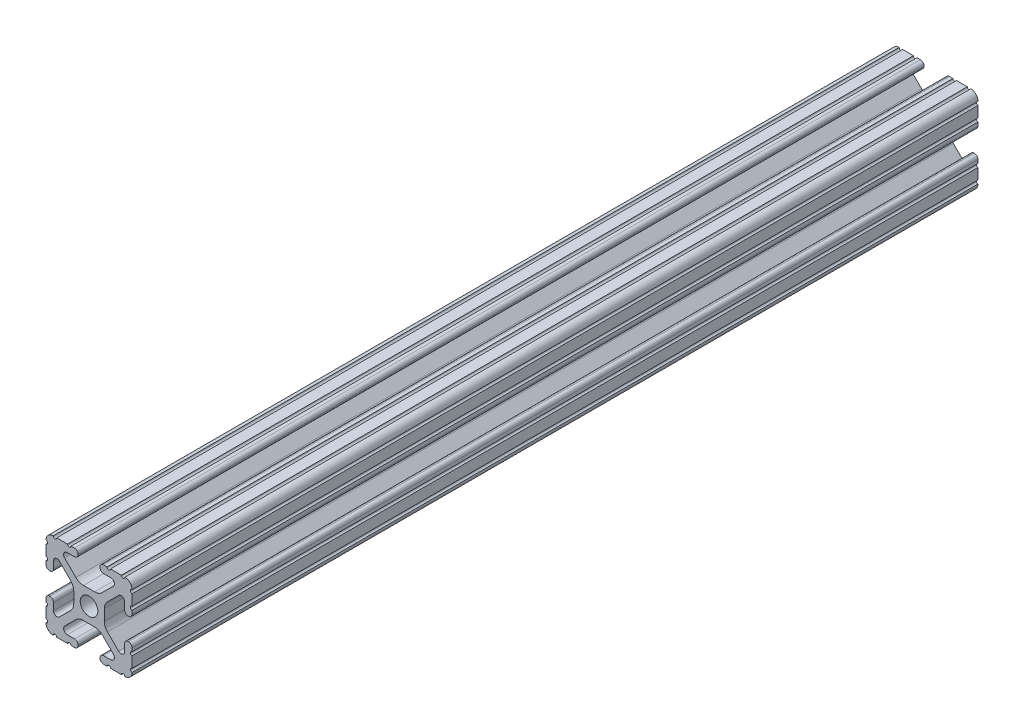
SolidWorks part; units mm, degrees
ref_plane "Front Plane" through (0, 0, 0) normal (0, 0, 1) x (1, 0, 0)
ref_plane "Top Plane" through (0, 0, 0) normal (0, 1, 0) x (1, 0, 0)
ref_plane "Right Plane" through (0, 0, 0) normal (1, 0, 0) x (0, 0, -1)
sketch "Sketch1" plane through (0, 0, 0) normal (0, 0, 1) x (1, 0, 0)
  line L88 (-7.1797, -8.6452) -> (-3.9523, -5.4237)
  line L89 (-1.7093, -4.4958) -> (1.7093, -4.4958)
  line L90 (3.9523, -5.4237) -> (7.1797, -8.6452)
  line L91 (6.4164, -10.4902) -> (4.2875, -10.4902)
  line L92 (3.2385, -11.5392) -> (3.2385, -11.651)
  line L93 (4.2875, -12.7) -> (5.3171, -12.7)
  line L94 (6.3331, -12.7) -> (9.5504, -12.7)
  line L95 (12.7, -9.5504) -> (12.7, -6.3331)
  line L96 (12.7, -5.3171) -> (12.7, -4.2875)
  line L97 (11.651, -3.2385) -> (11.5392, -3.2385)
  line L98 (10.4902, -4.2875) -> (10.4902, -6.4021)
  line L99 (8.7371, -7.1294) -> (5.441, -3.8408)
  line L100 (4.5085, -1.5932) -> (4.5085, 1.5932)
  line L101 (5.441, 3.8408) -> (8.7371, 7.1294)
  line L102 (10.4902, 6.4021) -> (10.4902, 4.2875)
  line L103 (11.5392, 3.2385) -> (11.651, 3.2385)
  line L104 (12.7, 4.2875) -> (12.7, 5.3171)
  line L105 (12.7, 6.3331) -> (12.7, 9.5504)
  line L106 (9.5504, 12.7) -> (6.3331, 12.7)
  line L107 (5.3171, 12.7) -> (4.2875, 12.7)
  line L108 (3.2385, 11.651) -> (3.2385, 11.5392)
  line L109 (4.2875, 10.4902) -> (6.4768, 10.4902)
  line L110 (7.207, 8.7244) -> (3.8983, 5.4232)
  line L111 (1.6558, 4.4958) -> (-1.6558, 4.4958)
  line L112 (-3.8983, 5.4232) -> (-7.207, 8.7244)
  line L113 (-6.4768, 10.4902) -> (-4.2875, 10.4902)
  line L114 (-3.2385, 11.5392) -> (-3.2385, 11.651)
  line L115 (-4.2875, 12.7) -> (-5.3171, 12.7)
  line L116 (-6.3331, 12.7) -> (-9.5504, 12.7)
  line L117 (-12.7, 9.5504) -> (-12.7, 6.3331)
  line L118 (-12.7, 5.3171) -> (-12.7, 4.2875)
  line L119 (-11.651, 3.2385) -> (-11.5392, 3.2385)
  line L120 (-10.4902, 4.2875) -> (-10.4902, 6.4021)
  line L121 (-8.7371, 7.1294) -> (-5.441, 3.8408)
  line L122 (-4.5085, 1.5932) -> (-4.5085, -1.5932)
  line L123 (-5.441, -3.8408) -> (-8.7371, -7.1294)
  line L124 (-10.4902, -6.4021) -> (-10.4902, -4.2875)
  line L125 (-11.5392, -3.2385) -> (-11.651, -3.2385)
  line L126 (-12.7, -4.2875) -> (-12.7, -5.3171)
  line L127 (-12.7, -6.3331) -> (-12.7, -9.5504)
  line L128 (-9.5504, -12.7) -> (-6.3331, -12.7)
  line L129 (-5.3171, -12.7) -> (-4.2875, -12.7)
  line L130 (-3.2385, -11.651) -> (-3.2385, -11.5392)
  line L131 (-4.2875, -10.4902) -> (-6.4164, -10.4902)
  circle A1 centre (0, 0) radius 2.6035
  arc A104 (-7.1797, -8.6452) -> (-6.4164, -10.4902) centre (-6.4164, -9.4098) ccw
  arc A105 (-1.7093, -4.4958) -> (-3.9523, -5.4237) centre (-1.7093, -7.6708) ccw
  arc A106 (3.9523, -5.4237) -> (1.7093, -4.4958) centre (1.7093, -7.6708) ccw
  arc A107 (6.4164, -10.4902) -> (7.1797, -8.6452) centre (6.4164, -9.4098) ccw
  arc A108 (4.2875, -10.4902) -> (3.2385, -11.5392) centre (4.2875, -11.5392) ccw
  arc A109 (3.2385, -11.651) -> (4.2875, -12.7) centre (4.2875, -11.651) ccw
  arc A110 (6.3331, -12.7) -> (5.3171, -12.7) centre (5.8251, -12.7) ccw
  arc A111 (10.5664, -12.6998) -> (9.5504, -12.7) centre (10.0584, -12.7) ccw
  arc A112 (10.5664, -12.6998) -> (12.6998, -10.5664) centre (10.5918, -10.5918) ccw
  arc A113 (12.7, -9.5504) -> (12.6998, -10.5664) centre (12.7, -10.0584) ccw
  arc A114 (12.7, -5.3171) -> (12.7, -6.3331) centre (12.7, -5.8251) ccw
  arc A115 (12.7, -4.2875) -> (11.651, -3.2385) centre (11.651, -4.2875) ccw
  arc A116 (11.5392, -3.2385) -> (10.4902, -4.2875) centre (11.5392, -4.2875) ccw
  arc A117 (8.7371, -7.1294) -> (10.4902, -6.4021) centre (9.4628, -6.4021) ccw
  arc A118 (4.5085, -1.5932) -> (5.441, -3.8408) centre (7.6835, -1.5932) ccw
  arc A119 (5.441, 3.8408) -> (4.5085, 1.5932) centre (7.6835, 1.5932) ccw
  arc A120 (10.4902, 6.4021) -> (8.7371, 7.1294) centre (9.4628, 6.4021) ccw
  arc A121 (10.4902, 4.2875) -> (11.5392, 3.2385) centre (11.5392, 4.2875) ccw
  arc A122 (11.651, 3.2385) -> (12.7, 4.2875) centre (11.651, 4.2875) ccw
  arc A123 (12.7, 6.3331) -> (12.7, 5.3171) centre (12.7, 5.8251) ccw
  arc A124 (12.6998, 10.5664) -> (12.7, 9.5504) centre (12.7, 10.0584) ccw
  arc A125 (12.6998, 10.5664) -> (10.5664, 12.6998) centre (10.5918, 10.5918) ccw
  arc A126 (9.5504, 12.7) -> (10.5664, 12.6998) centre (10.0584, 12.7) ccw
  arc A127 (5.3171, 12.7) -> (6.3331, 12.7) centre (5.8251, 12.7) ccw
  arc A128 (4.2875, 12.7) -> (3.2385, 11.651) centre (4.2875, 11.651) ccw
  arc A129 (3.2385, 11.5392) -> (4.2875, 10.4902) centre (4.2875, 11.5392) ccw
  arc A130 (7.207, 8.7244) -> (6.4768, 10.4902) centre (6.4768, 9.4563) ccw
  arc A131 (1.6558, 4.4958) -> (3.8983, 5.4232) centre (1.6558, 7.6708) ccw
  arc A132 (-3.8983, 5.4232) -> (-1.6558, 4.4958) centre (-1.6558, 7.6708) ccw
  arc A133 (-6.4768, 10.4902) -> (-7.207, 8.7244) centre (-6.4768, 9.4563) ccw
  arc A134 (-4.2875, 10.4902) -> (-3.2385, 11.5392) centre (-4.2875, 11.5392) ccw
  arc A135 (-3.2385, 11.651) -> (-4.2875, 12.7) centre (-4.2875, 11.651) ccw
  arc A136 (-6.3331, 12.7) -> (-5.3171, 12.7) centre (-5.8251, 12.7) ccw
  arc A137 (-10.5664, 12.6998) -> (-9.5504, 12.7) centre (-10.0584, 12.7) ccw
  arc A138 (-10.5664, 12.6998) -> (-12.6998, 10.5664) centre (-10.5918, 10.5918) ccw
  arc A139 (-12.7, 9.5504) -> (-12.6998, 10.5664) centre (-12.7, 10.0584) ccw
  arc A140 (-12.7, 5.3171) -> (-12.7, 6.3331) centre (-12.7, 5.8251) ccw
  arc A141 (-12.7, 4.2875) -> (-11.651, 3.2385) centre (-11.651, 4.2875) ccw
  arc A142 (-11.5392, 3.2385) -> (-10.4902, 4.2875) centre (-11.5392, 4.2875) ccw
  arc A143 (-8.7371, 7.1294) -> (-10.4902, 6.4021) centre (-9.4628, 6.4021) ccw
  arc A144 (-4.5085, 1.5932) -> (-5.441, 3.8408) centre (-7.6835, 1.5932) ccw
  arc A145 (-5.441, -3.8408) -> (-4.5085, -1.5932) centre (-7.6835, -1.5932) ccw
  arc A146 (-10.4902, -6.4021) -> (-8.7371, -7.1294) centre (-9.4628, -6.4021) ccw
  arc A147 (-10.4902, -4.2875) -> (-11.5392, -3.2385) centre (-11.5392, -4.2875) ccw
  arc A148 (-11.651, -3.2385) -> (-12.7, -4.2875) centre (-11.651, -4.2875) ccw
  arc A149 (-12.7, -6.3331) -> (-12.7, -5.3171) centre (-12.7, -5.8251) ccw
  arc A150 (-12.6998, -10.5664) -> (-12.7, -9.5504) centre (-12.7, -10.0584) ccw
  arc A151 (-12.6998, -10.5664) -> (-10.5664, -12.6998) centre (-10.5918, -10.5918) ccw
  arc A152 (-9.5504, -12.7) -> (-10.5664, -12.6998) centre (-10.0584, -12.7) ccw
  arc A153 (-5.3171, -12.7) -> (-6.3331, -12.7) centre (-5.8251, -12.7) ccw
  arc A154 (-4.2875, -12.7) -> (-3.2385, -11.651) centre (-4.2875, -11.651) ccw
  arc A155 (-3.2385, -11.5392) -> (-4.2875, -10.4902) centre (-4.2875, -11.5392) ccw
extrude "Boss-Extrude1" add sketch "Sketch1" along normal mid plane 609.6
sketch "Sketch2" plane through (12.7, 0, 0) normal (1, 0, 0) x (0, 0, -1)
  line L0 (-55.1236, -12.6998) -> (-55.1236, 13.5454) construction
  line L1 (-304.8, -12.6998) -> (304.8, -12.6998) construction
  line L2 (-55.1236, 13.5454) -> (-55.1236, -14.0971)
  line L3 (-55.1236, -14.0971) -> (307.535, -14.0971)
  line L4 (307.535, -14.0971) -> (307.535, 13.5454)
  line L5 (307.535, 13.5454) -> (-55.1236, 13.5454)
extrude "Cut-Extrude1" cut sketch "Sketch2" against normal blind 30.734 and the other way blind 7.112
